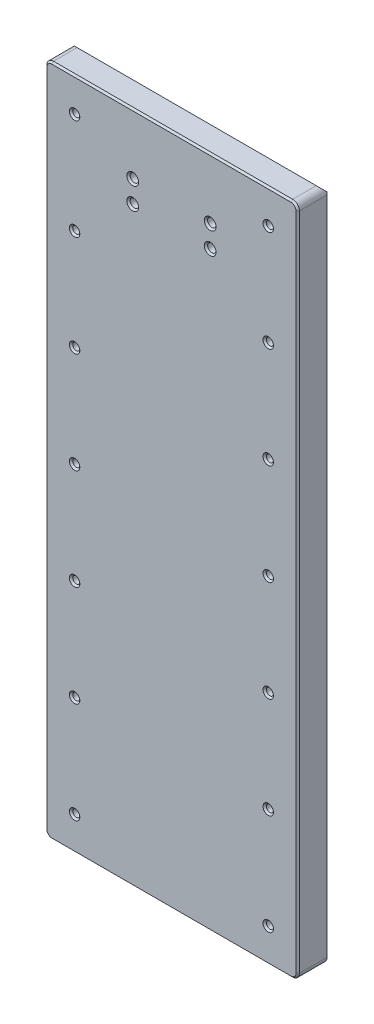
SolidWorks part; units mm, degrees
ref_plane "Front Plane" through (0, 0, 0) normal (0, 0, 1) x (1, 0, 0)
ref_plane "Top Plane" through (0, 0, 0) normal (0, 1, 0) x (1, 0, 0)
ref_plane "Right Plane" through (0, 0, 0) normal (1, 0, 0) x (0, 0, -1)
sketch "Sketch1" plane through (0, 0, 0) normal (0, 0, 1) x (1, 0, 0)
  line L1 (-14, 300) -> (136, 300)
  line L2 (-14, 300) -> (-14, -100)
  line L3 (-14, -100) -> (136, -100)
  line L4 (136, 300) -> (136, -100)
  dimension "D1" = 400
  dimension "D2" = 150
extrude "Boss-Extrude1" add sketch "Sketch1" along normal blind 18.5
sketch "Sketch10" plane through (0, 0, 18.5) normal (0, 0, 1) x (1, 0, 0)
  line L3 (104.1092, 305) -> (136, 300)
  line L4 (136, 300) -> (-14, 300)
  line L6 (17.8908, 305) -> (-14, 300)
  line L8 (61, 305) -> (17.8908, 305)
  line L9 (61, 305) -> (104.1092, 305)
sketch "Sketch2" plane through (0, 0, 0) normal (0, 0, 1) x (1, 0, 0)
  line L0 (61, 272) -> (28, 272)
  line L2 (28, 270) -> (28, 240)
  line L3 (28, 240) -> (94, 240)
  line L4 (94, 240) -> (94, 270)
  line L5 (94, 272) -> (61, 272)
  line L6 (28, 272) -> (28, 270)
  line L7 (94, 272) -> (94, 270)
extrude "Cut-Extrude1" cut sketch "Sketch2" along normal blind 11.5
fillet "Fillet1" radius 4 2 edges at (94, 240, 5.75) (28, 240, 5.75)
sketch "Sketch6" plane through (0, 0, 0) normal (0, 0, -1) x (-1, 0, 0)
  line L4 (-46, 240) -> (-76, 240)
  line L8 (-43, 240) -> (-46, 240)
  line L9 (-76, 240) -> (-79, 240)
  line L24 (-80, 240) -> (-80, 50)
  line L25 (-80, 50) -> (-80, 44)
  line L26 (-42, 50) -> (-42, 240)
  line L27 (-42, 50) -> (-42, 44)
  line L28 (-42, 44) -> (-42, -9)
  line L29 (-42, -25) -> (-42, -9)
  line L30 (-80, -25) -> (-42, -25)
  line L31 (-80, -9) -> (-80, -25)
  line L32 (-80, -9) -> (-80, 44)
  line L33 (-80, 240) -> (-79, 240)
  line L34 (-43, 240) -> (-42, 240)
extrude "Cut-Extrude3" cut sketch "Sketch6" against normal blind 8
sketch "Sketch7" plane through (0, 0, 11.5) normal (0, 0, -1) x (-1, 0, 0)
  circle A4 centre (-84, 264) radius 3.3
  circle A5 centre (-84, 251) radius 3.3
  circle A6 centre (-38, 251) radius 3.3
  circle A7 centre (-38, 264) radius 3.3
hole_wizard "M6x1.0 Tapped Hole1" positions "Sketch8" profile "Sketch9" tap size "M6x1.0" standard "ANSI Metric"
sketch "Sketch8" plane through (0, 0, 11.5) normal (0, 0, -1) x (-1, 0, 0)
  point P12 (-84, 264)
  point P15 (-38, 264)
  point P18 (-38, 251)
  point P21 (-84, 251)
sketch "Sketch9" plane through (84, 264, 11.5) normal (1, 0, 0) x (0, 1, 0)
  line L0 (0, 0) -> (0, 15)
  line L1 (0, 15) -> (2.5, 13.4978)
  line L2 (2.5, 13.4978) -> (2.5, 0)
  line L5 (2.5, 0) -> (0, 0)
  line L10 (0, 15) -> (-2.5, 13.4978) construction
  line L11 (0, -6.35) -> (0, 107.95) construction
  dimension "Tap Drill Dia." = 5
  dimension "Tap Drill Depth" = 15
  dimension "Drill Angle" = 118
cosmetic thread "Hole Thread7" parameters "D1"=12, "D2"=6
cosmetic thread "Hole Thread8" parameters "D1"=12, "D2"=6
cosmetic thread "Hole Thread9" parameters "D1"=12, "D2"=6
cosmetic thread "Hole Thread10" parameters "D1"=12, "D2"=6
sketch "Sketch11" plane through (0, 0, 0) normal (0, 0, -1) x (-1, 0, 0)
  line L2 (-61, 262) -> (-79, 262)
  line L3 (-61, 262) -> (-43, 262)
  line L4 (-43, 262) -> (-43, 273)
  line L5 (-47, 277) -> (-75, 277)
  line L6 (-79, 273) -> (-79, 262)
  arc A0 (-43, 273) -> (-47, 277) centre (-47, 273) ccw
  arc A1 (-75, 277) -> (-79, 273) centre (-75, 273) ccw
  dimension "D1" = 4
extrude "Cut-Extrude4" cut sketch "Sketch11" against normal up to surface (11.5 mm away) up to face at (81.5, 264, 11.5)
fillet "Fillet3" radius 4 4 edges at (79, 272, 5.75) (43, 272, 5.75) (94, 272, 5.75) (28, 272, 5.75)
sketch "Sketch12" plane through (0, 0, 0) normal (0, 0, -1) x (-1, 0, 0)
  line L0 (-3.5, -80) -> (-3.5, 280) construction
  line L1 (-118.5, -80) -> (-118.5, 280) construction
  line L2 (-3.5, -80) -> (-3.5, 280)
  line L3 (-118.5, -80) -> (-118.5, 280)
  circle A0 centre (-118.5, 280) radius 2.5
  circle A1 centre (-3.5, 280) radius 2.5
  circle A2 centre (-3.5, 220) radius 2.5
  circle A3 centre (-3.5, 160) radius 2.5
  circle A4 centre (-3.5, 100) radius 2.5
  circle A5 centre (-3.5, 40) radius 2.5
  circle A6 centre (-3.5, -20) radius 2.5
  circle A7 centre (-3.5, -80) radius 2.5
  circle A8 centre (-118.5, 220) radius 2.5
  circle A9 centre (-118.5, 160) radius 2.5
  circle A10 centre (-118.5, 100) radius 2.5
  circle A11 centre (-118.5, 40) radius 2.5
  circle A12 centre (-118.5, -20) radius 2.5
  circle A13 centre (-118.5, -80) radius 2.5
  dimension "D1" = 2
  dimension "D2" = 7
hole_wizard "M5x0.8 Tapped Hole1" positions "Sketch13" profile "Sketch14" tap size "M5x0.8" standard "ANSI Metric" end condition through all
sketch "Sketch13" plane through (0, 0, 0) normal (0, 0, -1) x (-1, 0, 0)
  point P0 (-118.5, 280)
  point P3 (-3.5, 280)
  point P6 (-118.5, 220)
  point P9 (-3.5, 220)
  point P12 (-3.5, 160)
  point P15 (-118.5, 160)
  point P18 (-118.5, 100)
  point P21 (-3.5, 100)
  point P24 (-3.5, 40)
  point P27 (-118.5, 40)
  point P30 (-3.5, -20)
  point P33 (-118.5, -20)
  point P36 (-118.5, -80)
  point P39 (-3.5, -80)
sketch "Sketch14" plane through (118.5, 280, 0) normal (1, 0, 0) x (0, 1, 0)
  line L0 (0, 0) -> (0, 18.5)
  line L1 (0, 18.5) -> (2.1, 18.5)
  line L2 (2.1, 18.5) -> (2.1, 0)
  line L5 (2.1, 0) -> (0, 0)
  line L11 (0, -6.35) -> (0, 107.95) construction
  dimension "Thru Tap Drill Dia." = 4.2
  dimension "Thru Tap Drill Depth" = 18.5
cosmetic thread "Hole Thread11" parameters "D2"=5
cosmetic thread "Hole Thread12" parameters "D2"=5
cosmetic thread "Hole Thread13" parameters "D2"=5
cosmetic thread "Hole Thread14" parameters "D2"=5
cosmetic thread "Hole Thread15" parameters "D2"=5
cosmetic thread "Hole Thread16" parameters "D2"=5
cosmetic thread "Hole Thread17" parameters "D2"=5
cosmetic thread "Hole Thread18" parameters "D2"=5
cosmetic thread "Hole Thread19" parameters "D2"=5
cosmetic thread "Hole Thread20" parameters "D2"=5
cosmetic thread "Hole Thread21" parameters "D2"=5
cosmetic thread "Hole Thread22" parameters "D2"=5
cosmetic thread "Hole Thread23" parameters "D2"=5
cosmetic thread "Hole Thread24" parameters "D2"=5
fillet "Fillet5" radius 4 4 edges at (-14, -100, 9.25) (136, -100, 9.25) (136, 300, 9.25) (-14, 300, 9.25)
chamfer "Chamfer2" distance 1 angle 45 26 edges at (-12.8284, 298.8284, 18.5) (61, 300, 18.5) (134.8284, 298.8284, 18.5) (136, 100, 18.5) (134.8284, -98.8284, 18.5) (61, -100, 18.5) (-12.8284, -98.8284, 18.5) (-14, 100, 18.5) (86.5, 251, 18.5) (40.5, 251, 18.5) (40.5, 264, 18.5) (86.5, 264, 18.5) (1.4, -80, 18.5) (116.4, -80, 18.5) (116.4, -20, 18.5) (1.4, -20, 18.5) (116.4, 40, 18.5) (1.4, 40, 18.5) (1.4, 100, 18.5) (116.4, 100, 18.5) (116.4, 160, 18.5) (1.4, 160, 18.5) (1.4, 220, 18.5) (116.4, 220, 18.5) (1.4, 280, 18.5) (116.4, 280, 18.5)
fillet "Fillet6" radius 4 4 edges at (42, 240, 4) (80, 240, 4) (42, -25, 4) (80, -25, 4)
chamfer "Chamfer3" distance 3 angle 45 21 edges at (41.8199, 272.6834, 0) (44.7639, 276.3166, 0) (61, 277, 0) (29.1716, 270.8284, 0) (77.2361, 276.3166, 0) (28, 256, 0) (80.1801, 272.6834, 0) (29.1716, 241.1716, 0) (35.7919, 272, 0) (35, 240, 0) (92.8284, 270.8284, 0) (40.8284, 238.8284, 0) (94, 256, 0) (42, 107.5, 0) (92.8284, 241.1716, 0) (43.1716, -23.8284, 0) (87, 240, 0) (61, -25, 0) (81.1716, 238.8284, 0) (78.8284, -23.8284, 0) (80, 107.5, 0)
chamfer "Chamfer4" distance 3.5 angle 45 1 edges at (61, 300, 0) tangent propagation no
chamfer "Chamfer5" distance 1 angle 45 7 edges at (135.9921, 296.2505, 0) (136, 100, 0) (134.8284, -98.8284, 0) (61, -100, 0) (-13.9921, 296.2505, 0) (-12.8284, -98.8284, 0) (-14, 100, 0)
